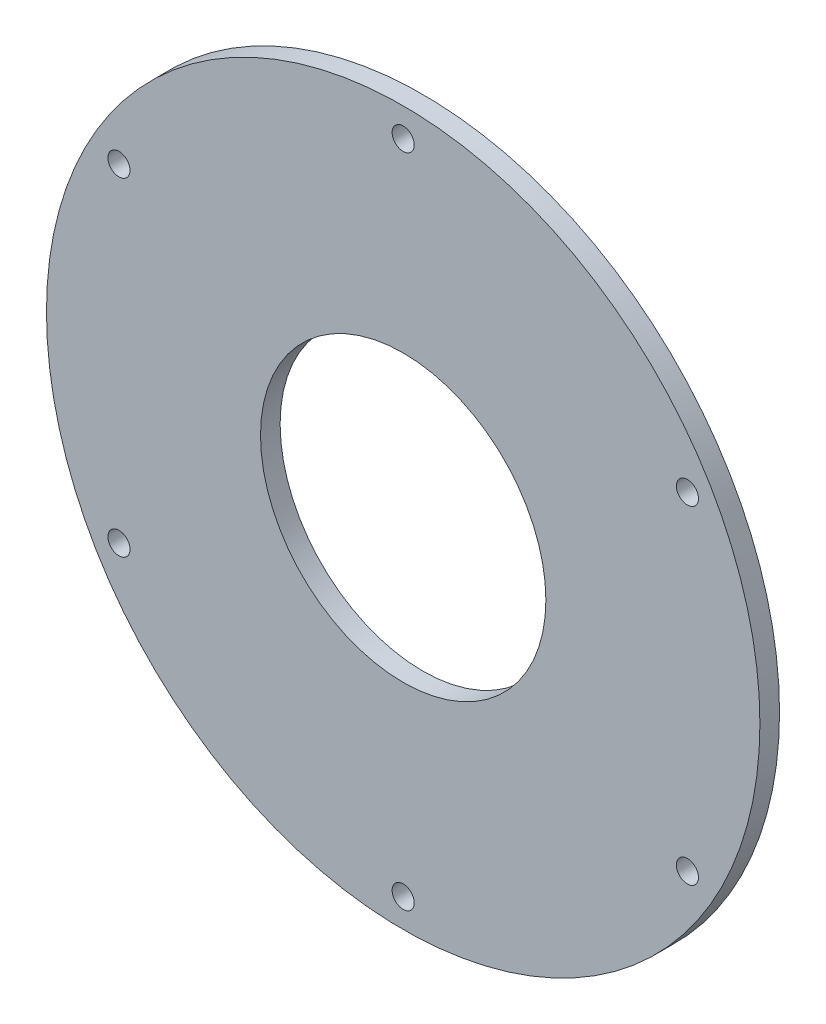
SolidWorks part; units mm, degrees
ref_plane "Ebene vorne" through (0, 0, 0) normal (0, 0, 1) x (1, 0, 0)
ref_plane "Ebene oben" through (0, 0, 0) normal (0, 1, 0) x (1, 0, 0)
ref_plane "Ebene rechts" through (0, 0, 0) normal (1, 0, 0) x (0, 0, -1)
sketch "Skizze1" plane through (0, 0, 0) normal (0, 0, 1) x (1, 0, 0)
  circle A0 centre (0, 0) radius 50
  circle A1 centre (0, 0) radius 20
  dimension "D1" = 100
  dimension "D2" = 40
extrude "Aufsatz-Linear austragen1" add sketch "Skizze1" along normal blind 2.75
hole_wizard "Ø3.1 (3.1) Durchmesser Bohrung1" positions "Skizze2" profile "Skizze3" hole size "Ø3.1" standard "ISO" end condition through all
sketch "Skizze2" plane through (0, 0, 2.75) normal (0, 0, 1) x (1, 0, 0)
  line L0 (0, 0) -> (0, -50000) construction
  circle A0 centre (0, 0) radius 46 construction
  circle A1 centre (0.0005, 0.0009) radius 46 construction
  circle A2 centre (0, 0.0017) radius 46 construction
  circle A3 centre (-0.001, 0.0017) radius 46 construction
  circle A4 centre (-0.0015, 0.0009) radius 46 construction
  circle A5 centre (-0.001, 0) radius 46 construction
  point P8 (0, 46)
  point P42 (39.8372, 23)
  point P43 (39.8372, -23)
  point P44 (0, -46)
  point P45 (-39.8372, -23)
  point P46 (-39.8372, 23)
  dimension "D1" = 92
  dimension "D2" = 6
  dimension "D3" = 6
sketch "Skizze3" plane through (-39.8372, 23, 2.75) normal (1, 0, 0) x (0, -1, 0)
  line L0 (0, 0) -> (0, 2.75)
  line L1 (0, 2.75) -> (1.55, 2.75)
  line L2 (1.55, 2.75) -> (1.55, 0)
  line L5 (1.55, 0) -> (0, 0)
  line L11 (0, -6.35) -> (0, 107.95) construction
  dimension "Bohrerdurchmesser" = 3.1
  dimension "Bohrungstiefe" = 2.75
